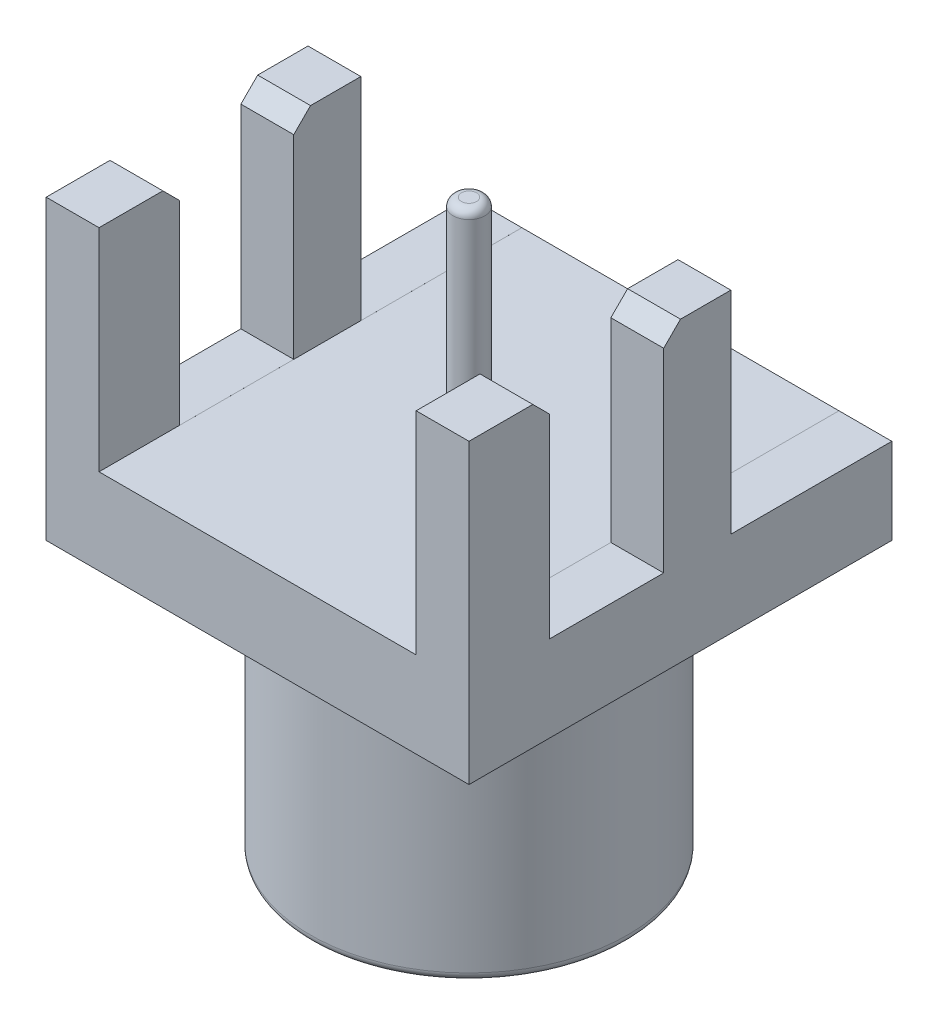
SolidWorks part; units mm, degrees
ref_plane "Front Plane" through (0, 0, 0) normal (0, 0, 1) x (1, 0, 0)
ref_plane "Top Plane" through (0, 0, 0) normal (0, 1, 0) x (1, 0, 0)
ref_plane "Right Plane" through (0, 0, 0) normal (1, 0, 0) x (0, 0, -1)
sketch "Sketch1" plane through (0, 0, 0) normal (0, 1, 0) x (1, 0, 0)
  line L1 (-3.2, -3.2) -> (3.2, -3.2)
  line L2 (-3.2, -3.2) -> (-3.2, 3.2)
  line L3 (-3.2, 3.2) -> (3.2, 3.2)
  line L4 (3.2, -3.2) -> (3.2, 3.2)
  line L5 (-3.2, -3.2) -> (3.2, 3.2) construction
  line L6 (-3.2, 3.2) -> (3.2, -3.2) construction
  point P0 (0, 0)
  dimension "D1" = 6.4
  dimension "D2" = 6.4
extrude "Boss-Extrude1" add sketch "Sketch1" along normal blind 1.3
sketch "Sketch2" plane through (0, 1.3, 0) normal (0, 1, 0) x (1, 0, 0)
  line L0 (-3.2, -3.2) -> (3.2, -3.2) construction
  line L1 (-3.2, 3.2) -> (-2.4, 3.2)
  line L2 (-3.2, 3.2) -> (-3.2, -3.2)
  line L3 (-3.2, -3.2) -> (-2.4, -3.2)
  line L4 (-2.4, 3.2) -> (-2.4, -3.2)
  line L6 (3.2, 3.2) -> (2.4, 3.2)
  line L7 (3.2, 3.2) -> (3.2, -3.2)
  line L8 (3.2, -3.2) -> (2.4, -3.2)
  line L9 (2.4, 3.2) -> (2.4, -3.2)
  dimension "D1" = 0.8
extrude "Boss-Extrude2" add sketch "Sketch2" along normal blind 0.0001
sketch "Sketch3" plane through (0, 1.3001, 0) normal (0, 1, 0) x (1, 0, 0)
  line L0 (-2.4, -3.2) -> (-2.4, 3.2) construction
  line L1 (-3.2, -3.2) -> (-2.4, -3.2)
  line L2 (-3.2, -3.2) -> (-3.2, -1.98)
  line L3 (-3.2, -1.98) -> (-2.4, -1.98)
  line L4 (-2.4, -3.2) -> (-2.4, -1.98)
  line L5 (-3.2, 3.2) -> (-3.2, -3.2) construction
  line L6 (-3.2, 0.7632) -> (-2.4, 0.7632)
  line L7 (-3.2, 0.7632) -> (-3.2, -0.2528)
  line L8 (-3.2, -0.2528) -> (-2.4, -0.2528)
  line L9 (-2.4, 0.7632) -> (-2.4, -0.2528)
  line L10 (0, 0) -> (0, -3.2) construction
  line L11 (-2.4, -3.2) -> (2.4, -3.2) construction
  line L12 (2.4, 0.7632) -> (2.4, -0.2528)
  line L13 (3.2, -0.2528) -> (2.4, -0.2528)
  line L14 (3.2, 0.7632) -> (3.2, -0.2528)
  line L15 (3.2, 0.7632) -> (2.4, 0.7632)
  line L16 (2.4, -3.2) -> (2.4, -1.98)
  line L17 (3.2, -1.98) -> (2.4, -1.98)
  line L18 (3.2, -3.2) -> (3.2, -1.98)
  line L19 (3.2, -3.2) -> (2.4, -3.2)
  dimension "D1" = 1.22
  dimension "D2" = 1.7272
  dimension "D3" = 1.016
extrude "Boss-Extrude3" add sketch "Sketch3" along normal blind 3.2
chamfer "Chamfer1" distance 0.254 angle 45 4 edges at (-2.8, 4.5001, 1.98) (2.8, 4.5001, 1.98) (2.8, 4.5001, 0.2528) (-2.8, 4.5001, 0.2528)
sketch "Sketch4" plane through (0, 1.3, 0) normal (0, 1, 0) x (1, 0, 0)
  circle A0 centre (0, 0) radius 0.24
  dimension "D1" = 0.48
extrude "Boss-Extrude4" add sketch "Sketch4" along normal up to surface (3.2001 mm away) up to face at (-2.8, 4.5001, -0.3822)
fillet "Fillet1" radius 0.125 1 edges at (0, 4.5001, 0.24)
sketch "Sketch5" plane through (0, 0, 0) normal (0, -1, 0) x (1, 0, 0)
  circle A0 centre (0, 0) radius 0.381
  circle A1 centre (0, 0) radius 2.0825
  circle A2 centre (0, 0) radius 2.4
  dimension "D1" = 0.762
  dimension "D2" = 4.8
  dimension "D3" = 0.3175
extrude "Boss-Extrude5" add sketch "Sketch5" along normal blind 4.1 contours A2 A1 | A0 region at (0, 0, 0) region at (-2.3321, 0, 0)
ref_axis "Axis1" through (0, -4.1, 0) along (0, 1, 0)
sketch "Sketch7" plane through (0, -4.1, 0) normal (0, -1, 0) x (1, 0, 0)
  circle A1 centre (0, 0) radius 0.381
  circle A2 centre (0, 0) radius 0.381
  dimension "D1" = 0
extrude "Cut-Extrude1" cut sketch "Sketch7" against normal blind 1.524
sketch "Sketch8" plane through (0, -2.576, 0) normal (0, -1, 0) x (1, 0, 0)
  circle A1 centre (0, 0) radius 0.381
  circle A2 centre (0, 0) radius 0.381
  dimension "D1" = 0
extrude "Boss-Extrude6" add sketch "Sketch8" along normal blind 0.762 draft 15
fillet "Fillet2" radius 0.127 1 edges at (0, -3.338, -0.1768)
fillet "Fillet3" radius 0.127 1 edges at (0, -4.1, -2.4)
